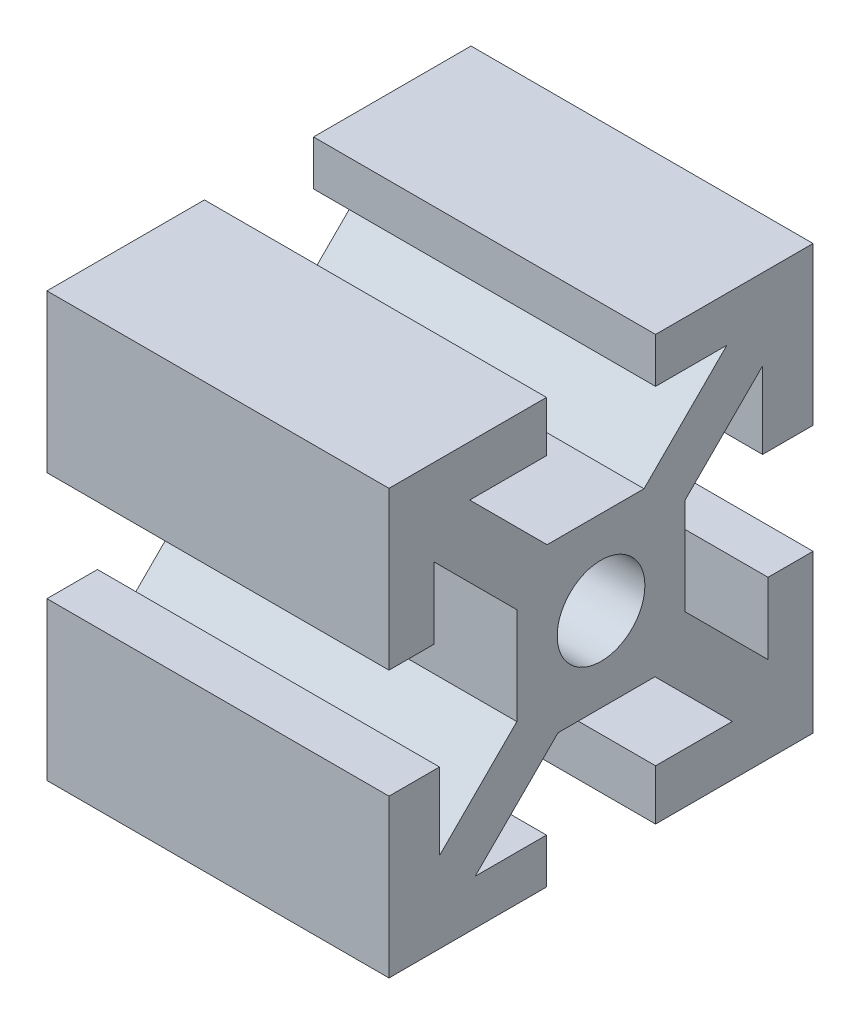
SolidWorks part; units mm, degrees
ref_plane "Front Plane" through (0, 0, 0) normal (0, 0, 1) x (1, 0, 0)
ref_plane "Top Plane" through (0, 0, 0) normal (0, 1, 0) x (1, 0, 0)
ref_plane "Right Plane" through (0, 0, 0) normal (1, 0, 0) x (0, 0, -1)
sketch "Sketch1" plane through (0, 0, 0) normal (1, 0, 0) x (0, 0, -1)
  line L0 (2.5534, 5) -> (7.4749, 9.9215)
  line L1 (-5, 5) -> (5, 5)
  line L2 (-5, 5) -> (-5, -5)
  line L3 (-5, -5) -> (5, -5)
  line L4 (5, 5) -> (5, -5)
  line L5 (-5, 5) -> (5, -5) construction
  line L6 (-5, -5) -> (5, 5) construction
  line L7 (7.4749, 9.9215) -> (9.5962, 7.8001)
  line L8 (9.5962, 7.8001) -> (5, 3.2039)
  line L9 (5, 5) -> (13.6489, 13.6489) construction
  line L10 (7.4749, 9.9215) -> (3.24, 9.9215)
  line L11 (3.24, 9.9215) -> (3.24, 12.5962)
  line L12 (3.24, 12.5962) -> (12.5962, 12.5962)
  line L13 (9.5962, 7.8001) -> (9.5962, 3.24)
  line L14 (9.5962, 3.24) -> (12.5962, 3.24)
  line L15 (12.5962, 3.24) -> (12.5962, 12.5962)
  line L17 (0, 0) -> (0, 24.089) construction
  line L18 (0, 0) -> (23.75, 0) construction
  circle A0 centre (0, 0) radius 2.605
  point P0 (0, 0)
  dimension "D1" = 5.21
  dimension "D2" = 10
  dimension "D3" = 10
  dimension "D4" = 3
  dimension "D5" = 1.27
  dimension "D6" = 6.5
  dimension "D7" = 3.24
  dimension "D8" = 3.24
  dimension "D9" = 3
extrude "Boss-Extrude1" add sketch "Sketch1" along normal blind 20.32 contours L4 L1 L2 L3 A0 | L8 L7 L0 L1 L4 | L14 L15 L12 L11 L10 L7 L13 region at (0, 4.8586, -3.7767) region at (0, 6.7479, -6.3823) region at (0, 9.18, -9.3105)
ref_axis "Axis1" through (0, 0, 0) along (1, 0, 0)
pattern_circular "CirPattern1" count 4 over 360 about axis through (0, 0, 0) along (1, 0, 0) of "Boss-Extrude1"
